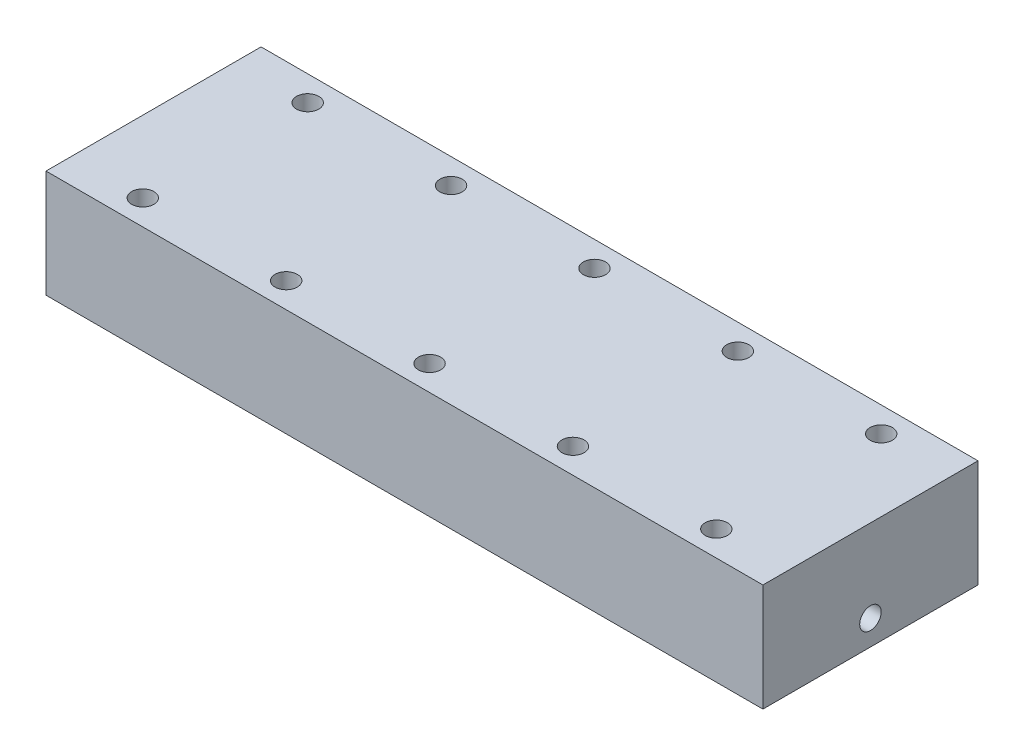
SolidWorks part; units mm, degrees
ref_plane "Front Plane" through (0, 0, 0) normal (0, 0, 1) x (1, 0, 0)
ref_plane "Top Plane" through (0, 0, 0) normal (0, 1, 0) x (1, 0, 0)
ref_plane "Right Plane" through (0, 0, 0) normal (1, 0, 0) x (0, 0, -1)
sketch "Sketch1" plane through (0, 0, 0) normal (0, 1, 0) x (1, 0, 0)
  line L0 (-50, 0) -> (50, 0)
  line L1 (50, 0) -> (50, 30)
  line L2 (50, 30) -> (-50, 30)
  line L3 (-50, 30) -> (-50, 0)
  dimension "D1" = 100
  dimension "D2" = 50
  dimension "D3" = 30
  dimension "D4" = 30
extrude "Boss-Extrude1" add sketch "Sketch1" along normal blind 15
sketch "Sketch2" plane through (0, 0, 0) normal (0, 1, 0) x (1, 0, 0)
  line L0 (45, 24) -> (45, 6)
  line L1 (45, 6) -> (15, 6)
  line L2 (15, 6) -> (15, 24)
  line L3 (15, 24) -> (45, 24)
  line L4 (-50, 0) -> (50, 0) construction
  line L6 (50, 0) -> (50, 30) construction
  dimension "D1" = 18
  dimension "D2" = 6
  dimension "D3" = 30
  dimension "D4" = 5
extrude "Cut-Extrude1" cut sketch "Sketch2" against normal blind 8.5 and the other way blind 8.5
sketch "Sketch4" plane through (0, 0, 0) normal (0, 1, 0) x (1, 0, 0)
  line L0 (15, 6) -> (25, 6)
  line L1 (45, 6) -> (15, 6) construction
  line L2 (25, 6) -> (25, 24)
  line L3 (15, 24) -> (45, 24) construction
  line L4 (25, 24) -> (15, 24)
  line L5 (15, 24) -> (15, 6)
  dimension "D1" = 10
extrude "Boss-Extrude2" add sketch "Sketch4" along normal blind 10
sketch "Sketch3" plane through (0, 0, 0) normal (0, 1, 0) x (1, 0, 0)
  line L0 (50, 15) -> (-50, 15) construction
  line L1 (50, 0) -> (50, 30) construction
  line L2 (-50, 30) -> (-50, 0) construction
  line L3 (-45, 15) -> (-45, 8.41)
  line L4 (-45, 8.41) -> (35, 6.89)
  line L5 (35, 6.89) -> (35, 15)
  line L6 (35, 15) -> (-45, 15)
  line L8 (25, 6) -> (25, 24) construction
  dimension "D1" = 80
  dimension "D3" = 8.11
  dimension "D4" = 6.59
  dimension "D5" = 10
revolve "Cut-Revolve1" cut sketch "Sketch3" angle 360 about L0
sketch "Sketch6" plane through (0, 0, 0) normal (0, 1, 0) x (1, 0, 0)
  line L0 (-50, 15) -> (47.3429, 15) construction
  line L1 (-50, 30) -> (-50, 0) construction
  line L2 (25, 22.92) -> (25, 20.42)
  line L3 (25, 20.42) -> (15.0477, 20.23)
  line L4 (15.0477, 20.23) -> (15, 22.73)
  line L5 (-45, 21.59) -> (25, 22.92) construction
  line L6 (15, 22.73) -> (25, 22.92)
  dimension "D1" = 10
  dimension "D2" = 2.5
  dimension "D3" = 2.5
revolve "Revolve1" add sketch "Sketch6" angle 180 about L0
sketch "Sketch7" plane through (0, 0, 0) normal (0, 1, 0) x (1, 0, 0)
  line L0 (-45, 15) -> (38.1554, 15) construction
  line L1 (-45, 8.41) -> (-45, 21.59) construction
  line L2 (-35, 21.78) -> (-22.5, 22.0175)
  line L3 (-45, 21.59) -> (15, 22.73) construction
  line L4 (-22.5, 22.0175) -> (-22.5, 19.5175)
  line L5 (-22.5, 19.5175) -> (-35, 19.28)
  line L6 (-35, 19.28) -> (-35, 21.78)
  dimension "D1" = 2.5
  dimension "D2" = 2.5
  dimension "D3" = 12.5
  dimension "D4" = 10
revolve "Revolve2" add sketch "Sketch7" angle 180 about L0
sketch "Sketch8" plane through (0, 0, 0) normal (0, 1, 0) x (1, 0, 0)
  line L0 (-45, 15) -> (32.5702, 15) construction
  line L1 (-45, 8.41) -> (-45, 21.59) construction
  line L2 (-10, 22.255) -> (-10, 19.755)
  line L3 (-22.5, 22.0175) -> (15, 22.73) construction
  line L4 (-10, 19.755) -> (2.5, 19.9925)
  line L5 (2.5, 19.9925) -> (2.5, 22.4925)
  line L6 (2.5, 22.4925) -> (-10, 22.255)
  dimension "D1" = 12.5
  dimension "D2" = 2.5
  dimension "D3" = 2.5
  dimension "D4" = 12.5
revolve "Revolve3" add sketch "Sketch8" angle 180 about L0
ref_plane "Plane1" through (-50, 0, 0) normal (-1, 0, 0) x (0, 0, 1)
sketch "Sketch9" plane through (-50, 0, 0) normal (-1, 0, 0) x (0, 0, 1)
  line L0 (0, 15) -> (0, 0) construction
  line L1 (-30, 0) -> (0, 0) construction
  circle A0 centre (-15, 3.5) radius 1
  dimension "D2" = 2
  dimension "D1" = 15
  dimension "D3" = 3.5
extrude "Cut-Extrude2" cut sketch "Sketch9" against normal blind 12
ref_plane "Plane2" through (50, 0, 0) normal (1, 0, 0) x (0, 0, -1)
sketch "Sketch10" plane through (50, 0, 0) normal (1, 0, 0) x (0, 0, -1)
  circle A0 centre (15, 3.5) radius 1.5
  dimension "D1" = 3
extrude "Cut-Extrude3" cut sketch "Sketch10" against normal blind 12
fillet "Fillet3" radius 1.2 10 edges at (15.0477, 5.23, -15) (15, 7.73, -15) (-10, 7.255, -15) (2.5, 7.4925, -15) (2.5, 4.9925, -15) (-10, 4.755, -15) (-22.5, 7.0175, -15) (-22.5, 4.5175, -15) (-35, 6.78, -15) (-35, 4.28, -15)
fillet "Fillet5" radius 1.25 1 edges at (25, 5.42, -15)
fillet "Fillet7" radius 2 8 edges at (25, 4.25, -24) (25, 4.25, -6) (45, 4.25, -24) (35, 8.5, -24) (45, 4.25, -6) (45, 8.5, -15) (35, 8.5, -6) (25, 8.5, -15)
sketch "Sketch11" plane through (0, 0, 0) normal (0, 1, 0) x (1, 0, 0)
  line L0 (-50, 8.25) -> (-50, -8.25) construction
  line L2 (-50, 0) -> (50, 0) construction
  line L3 (-50, 0) -> (50, 0) construction
  line L4 (50, 30) -> (-50, 30) construction
  line L5 (-50, 30) -> (-50, 0) construction
  circle A0 centre (-40, 3.5) radius 1.55
  circle A1 centre (-20, 3.5) radius 1.55
  circle A2 centre (0, 3.5) radius 1.55
  circle A3 centre (20, 3.5) radius 1.55
  circle A4 centre (40, 3.5) radius 1.55
  circle A5 centre (-40, 26.5) radius 1.55
  circle A6 centre (-20, 26.5) radius 1.55
  circle A7 centre (0, 26.5) radius 1.55
  circle A8 centre (20, 26.5) radius 1.55
  circle A9 centre (40, 26.5) radius 1.55
  dimension "D11" = 3.1
  dimension "D12" = 3.1
  dimension "D13" = 3.1
  dimension "D14" = 3.1
  dimension "D15" = 3.1
  dimension "D17" = 3.1
  dimension "D18" = 3.1
  dimension "D21" = 3.1
  dimension "D23" = 3.1
  dimension "D25" = 3.1
  dimension "D1" = 10
  dimension "D2" = 20
  dimension "D3" = 20
  dimension "D4" = 20
  dimension "D5" = 20
  dimension "D6" = 3.5
  dimension "D7" = 3.5
  dimension "D8" = 3.5
  dimension "D9" = 3.5
  dimension "D10" = 3.5
  dimension "D16" = 3.5
  dimension "D19" = 3.5
  dimension "D20" = 3.5
  dimension "D22" = 3.5
  dimension "D24" = 3.5
  dimension "D26" = 10
  dimension "D27" = 20
  dimension "D28" = 20
  dimension "D29" = 20
  dimension "D30" = 20
extrude "Cut-Extrude4" cut sketch "Sketch11" against normal blind 20 and the other way blind 20
